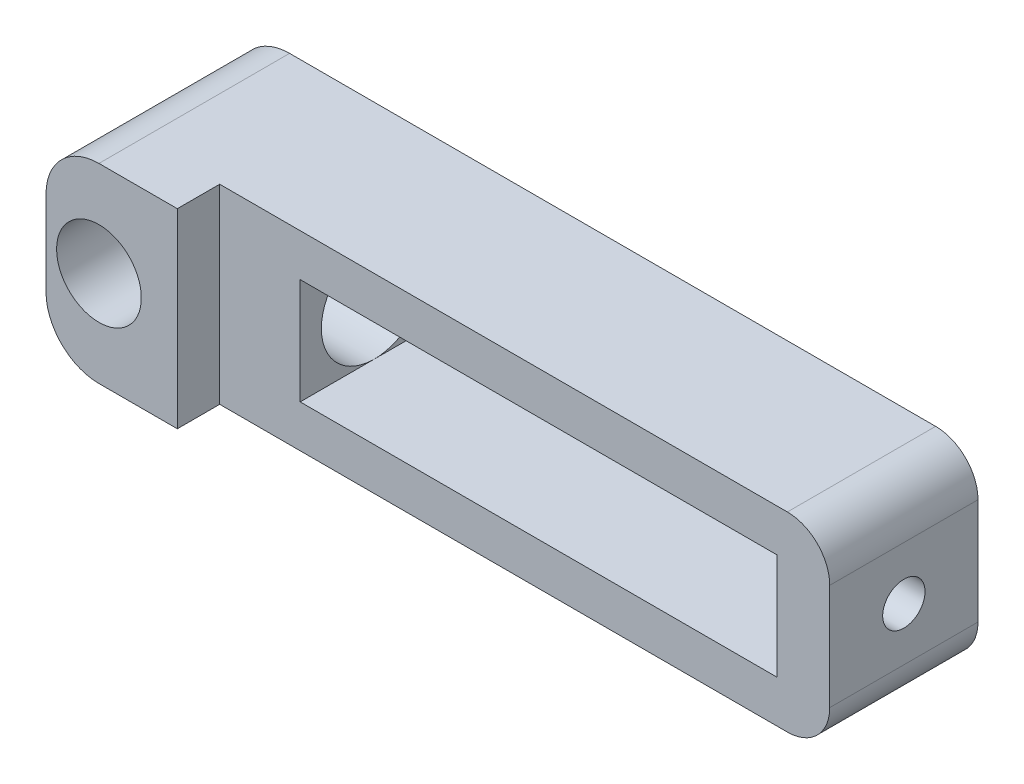
SolidWorks part; units mm, degrees
material "3003 合金"
ref_plane "前视基准面" through (0, 0, 0) normal (0, 0, 1) x (1, 0, 0)
ref_plane "上视基准面" through (0, 0, 0) normal (0, 1, 0) x (1, 0, 0)
ref_plane "右视基准面" through (0, 0, 0) normal (1, 0, 0) x (0, 0, -1)
sketch "草图1" plane through (0, 0, 0) normal (0, 0, 1) x (1, 0, 0)
  line L1 (0, 0) -> (35, 0)
  line L2 (0, 0) -> (0, -9)
  line L3 (0, -9) -> (35, -9)
  line L4 (35, 0) -> (35, -9)
  line L5 (10, -2) -> (32.5, -2)
  line L6 (10, -2) -> (10, -7)
  line L7 (10, -7) -> (32.5, -7)
  line L8 (32.5, -2) -> (32.5, -7)
  circle A0 centre (2.5, -4.5) radius 2
  dimension "D7" = 2.5
  dimension "D8" = 4.5
  dimension "D9" = 4
  dimension "D1" = 9
  dimension "D2" = 35
  dimension "D3" = 2
  dimension "D4" = 2
  dimension "D5" = 10
  dimension "D6" = 2.5
extrude "凸台-拉伸1" add sketch "草图1" along normal blind 7
sketch "草图2" plane through (0, 0, 7) normal (0, 0, 1) x (1, 0, 0)
  line L0 (0, -9) -> (35, -9) construction
  line L1 (0, 0) -> (6.2, 0)
  line L2 (0, 0) -> (0, -9)
  line L3 (0, -9) -> (6.2, -9)
  line L4 (6.2, 0) -> (6.2, -9)
  circle A1 centre (2.5, -4.5) radius 2
  dimension "D1" = 3.7
extrude "凸台-拉伸2" add sketch "草图2" along normal blind 4.5
sketch "草图3" plane through (35, 0, 0) normal (1, 0, 0) x (0, 0, -1)
  line L0 (-7, -9) -> (0, -9) construction
  line L1 (0, -9) -> (0, 0) construction
  circle A0 centre (-3.5, -4.5) radius 1
  dimension "D1" = 4.5
  dimension "D2" = 3.5
  dimension "D3" = 2
extrude "切除-拉伸2" cut sketch "草图3" against normal up to next
sketch "草图5" plane through (10, 0, 0) normal (1, 0, 0) x (0, 0, -1)
  circle A0 centre (-3.5, -4.5) radius 2.5
  dimension "D1" = 5
extrude "切除-拉伸4" cut sketch "草图5" against normal up to next
fillet "圆角1" radius 2 2 edges at (35, -9, 3.5) (35, 0, 3.5)
sketch "草图10" plane through (0, 0, 11.5) normal (0, 0, 1) x (1, 0, 0)
  line L1 (0, -9) -> (6.2, -9)
  line L2 (0, -9) -> (0, 0)
  line L3 (0, 0) -> (6.2, 0)
  line L4 (6.2, -9) -> (6.2, 0)
extrude "切除-拉伸7" cut sketch "草图10" against normal blind 2.5
fillet "圆角3" radius 2.5 2 edges at (0, 0, 4.5) (0, -9, 4.5)
